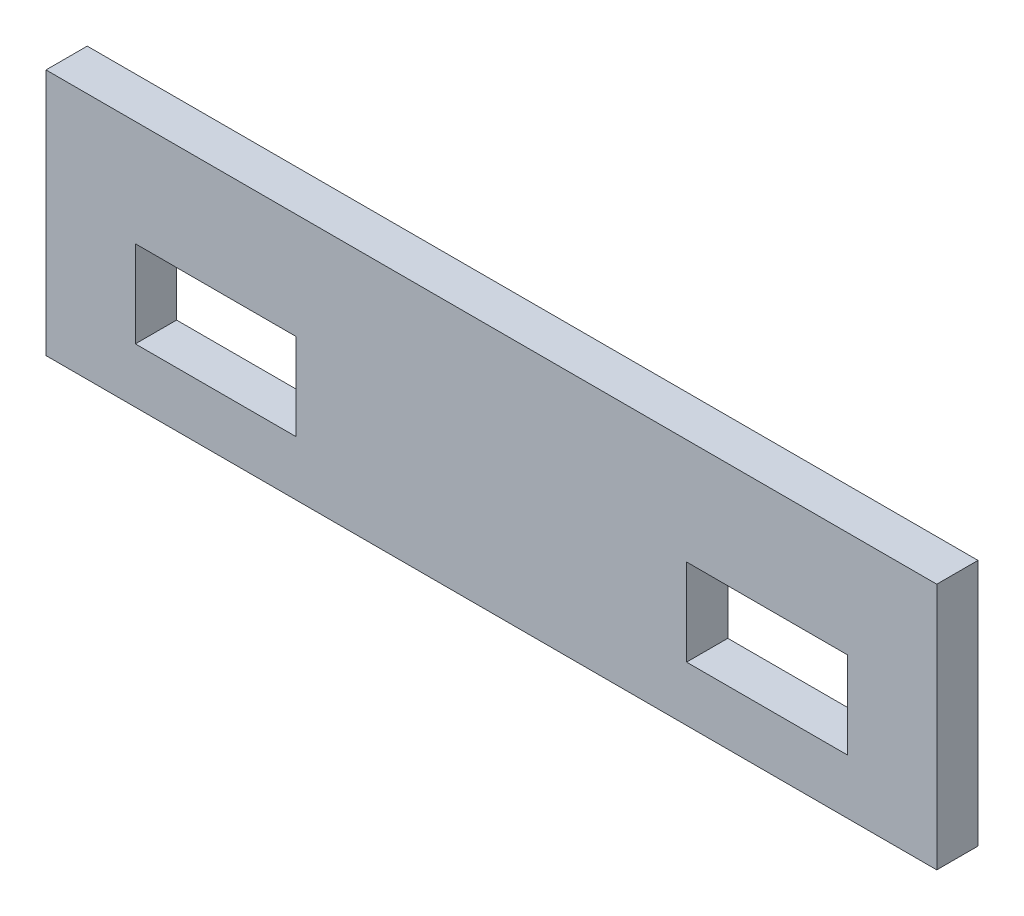
SolidWorks part; units mm, degrees
ref_plane "Front Plane" through (0, 0, 0) normal (0, 0, 1) x (1, 0, 0)
ref_plane "Top Plane" through (0, 0, 0) normal (0, 1, 0) x (1, 0, 0)
ref_plane "Right Plane" through (0, 0, 0) normal (1, 0, 0) x (0, 0, -1)
sketch "SK_Body" plane through (0, 0, 0) normal (0, 0, 1) x (1, 0, 0)
  line L1 (-162, 0) -> (162, 0)
  line L2 (-162, 0) -> (-162, 90)
  line L3 (-162, 90) -> (162, 90)
  line L4 (162, 0) -> (162, 90)
  dimension "D1" = 324
  dimension "D2" = 90
  dimension "D3" = 162
extrude "EX_Body" add sketch "SK_Body" along normal blind 15
sketch "SK_SwitchPockets" plane through (0, 0, 0) normal (0, 0, 1) x (1, 0, 0)
  line L1 (45, 39) -> (65, 39)
  line L2 (45, 39) -> (45, 51)
  line L3 (45, 51) -> (65, 51)
  line L4 (65, 39) -> (65, 51)
  line L6 (-65, 39) -> (-45, 39)
  line L7 (-65, 39) -> (-65, 51)
  line L8 (-65, 51) -> (-45, 51)
  line L9 (-45, 39) -> (-45, 51)
  dimension "D1" = 20
  dimension "D2" = 12
  dimension "D3" = 45
  dimension "D4" = 39
  dimension "D5" = 20
  dimension "D6" = 12
  dimension "D7" = 65
  dimension "D8" = 39
extrude "CUT_SwitchPockets" cut sketch "SK_SwitchPockets" along normal blind 8
sketch "SK_GuidePins" plane through (0, 0, 0) normal (0, 0, 1) x (1, 0, 0)
  circle A0 centre (150, 20) radius 2.5
  circle A1 centre (-150, 20) radius 2.5
  dimension "D3" = 5
  dimension "D6" = 5
  dimension "D1" = 150
  dimension "D2" = 20
  dimension "D4" = 150
  dimension "D5" = 20
extrude "CUT_GuidePins" cut sketch "SK_GuidePins" along normal blind 10
sketch "SK_CliffWindows" plane through (0, 0, 0) normal (0, 0, 1) x (1, 0, 0)
  line L1 (71, 19.9474) -> (129.5, 19.9474)
  line L2 (71, 19.9474) -> (71, 51.5)
  line L3 (71, 51.5) -> (129.5, 51.5)
  line L4 (129.5, 19.9474) -> (129.5, 51.5)
  line L6 (-129.5, 19.9474) -> (-71, 19.9474)
  line L7 (-129.5, 19.9474) -> (-129.5, 51.5)
  line L8 (-129.5, 51.5) -> (-71, 51.5)
  line L9 (-71, 19.9474) -> (-71, 51.5)
  dimension "D1" = 58.5
  dimension "D2" = 31.5526
  dimension "D3" = 71
  dimension "D4" = 19.9474
  dimension "D5" = 58.5
  dimension "D6" = 31.5526
  dimension "D7" = 129.5
  dimension "D8" = 19.9474
extrude "CUT_CliffWindows" cut sketch "SK_CliffWindows" along normal blind 15
ref_axis "AX_X" through (0, 0, -0.75) along (0, 0, 1)
ref_axis "AX_Y" through (178.2, 0, 0) along (-1, 0, 0)
ref_axis "AX_Z" through (0, 94.5, 0) along (0, -1, 0)
equation "\"BODY_L\"= 420"
equation "\"BODY_W\"= 340"
equation "\"FLOOR_Z\"= 35"
equation "\"DECK_Z\"= 180"
equation "\"DECK_T\"= 2"
equation "\"GRID\"= 20"
equation "\"PROFILE\"= 20"
equation "\"SM_T\"= 1.5"
equation "\"PAN_T\"= 1.5"
equation "\"PAN_TOP\"= \"FLOOR_Z\" + \"PAN_T\""
equation "\"RAIL_Y\"= 140"
equation "\"RAIL_X\"= \"BODY_L\" / 2 - \"PROFILE\" / 2 - 2"
equation "\"BOTRING_Z\"= \"PAN_TOP\" + \"PROFILE\" / 2"
equation "\"TOPRING_Z\"= \"DECK_Z\" - \"DECK_T\" - \"PROFILE\" / 2"
equation "\"DRAWER_Z\"= 93"
equation "\"MIDX_Z\"= \"DRAWER_Z\" - \"SM_T\" - \"PROFILE\" / 2"
equation "\"SKIN_Y\"= \"RAIL_Y\" + \"PROFILE\" / 2"
equation "\"SKIN_T\"= 2"
equation "\"WHEEL_D\"= 144"
equation "\"WHEEL_W\"= 52"
equation "\"TRACK\"= 365"
equation "\"AXLE_Z\"= \"WHEEL_D\" / 2"
equation "\"WHEEL_WEB_OFF\"= 6"
equation "\"HUB_T\"= 8"
equation "\"BUSHING_L\"= 6"
equation "\"HUB_GAP\"= 1"
equation "\"MOTOR_UP\"= 7"
equation "\"MOTOR_FACE_Y\"= \"TRACK\" / 2 + \"WHEEL_WEB_OFF\" - (\"BUSHING_L\" + \"HUB_GAP\" + \"HUB_T\")"
equation "\"MOTOR_AXIS_Z\"= \"AXLE_Z\" + \"MOTOR_UP\""
equation "\"CASTER_D\"= 50"
equation "\"CASTER_X\"= 150"
equation "\"CASTER_H\"= 68"
equation "\"POST_X\"= -40"
equation "\"POST_DY\"= 120"
equation "\"POST_SIZE\"= 20"
equation "\"POST_TOP\"= 400"
equation "\"BRACE_Z\"= 335"
equation "\"STRUT_X0\"= -140"
equation "\"HEAD_X0\"= -110"
equation "\"HEAD_X1\"= 12"
equation "\"BEZEL_T\"= 3"
equation "\"WEDGE_MID\"= 7.7"
equation "\"OAK_D\"= 22.9"
equation "\"HEAD_W\"= 210"
equation "\"HEAD_Z0\"= \"POST_TOP\""
equation "\"HEAD_TOP\"= 525"
equation "\"HEAD_TOP_X\"= -20"
equation "\"SCREEN_ANG\"= 35"
equation "\"LENS_X\"= 45.6"
equation "\"LENS_Z\"= 450"
equation "\"OAK_TILT\"= 5"
equation "\"OAK_VFOV_DEPTH\"= 79.5"
equation "\"OAK_VFOV_RGB\"= 72"
equation "\"LIDAR_X\"= 110"
equation "\"SCAN_Z\"= 260"
equation "\"STRUT_Z\"= \"SCAN_Z\" - 20"
equation "\"LIDAR_SCAN_H\"= 27.2"
equation "\"LIDAR_MOUNT_Z\"= \"SCAN_Z\" - \"LIDAR_SCAN_H\""
equation "\"ESTOP_X\"= -172.5"
equation "\"ESTOP_Y\"= -127.5"
equation "\"ESTOP_TOP\"= 225"
equation "\"BUMPER_T\"= 15"
equation "\"BUMPER_Z0\"= 40"
equation "\"BUMPER_Z1\"= 130"
equation "\"CLIFF_X\"= 218"
equation "\"CLIFF_Y\"= 105"
equation "\"CLIFF_Z\"= 72"
equation "\"CLIFF_ANG\"= 50"
equation "\"CONTACT_X\"= 216"
equation "\"CONTACT_Y\"= 64"
equation "\"CONTACT_Z\"= 30"
equation "\"DOCK_TAG_DIST\"= 250"
equation "\"DOCK_TAG_SIZE\"= 80"
equation "\"DOCK_TAG_Z\"= 400"
equation "\"BAT_L\"= 240"
equation "\"BAT_W\"= 90"
equation "\"BAT_H\"= 58"
equation "\"BAT_Z\"= \"DRAWER_Z\" + \"SM_T\""
equation "\"BAT_X\"= 0"
equation "\"PCB_L\"= 95"
equation "\"PCB_W\"= 120"
equation "\"PCB_H\"= 40"
equation "\"PCB_X\"= 62.5"
equation "\"DRV_X\"= 85"
equation "\"DRV_Y\"= 100"
equation "\"DRV_S\"= 50"
equation "\"COMPUTE_X\"= -65"
equation "\"COMPUTE_L\"= 90"
equation "\"COMPUTE_W\"= 160"
equation "\"D1@SK_Body\" = \"BODY_W\" - 16"
equation "\"D2@SK_Body\" = \"BUMPER_Z1\" - \"BUMPER_Z0\""
equation "\"D3@SK_Body\" = \"BODY_W\" / 2 - 8"
equation "\"D1@EX_Body\" = \"BUMPER_T\""
